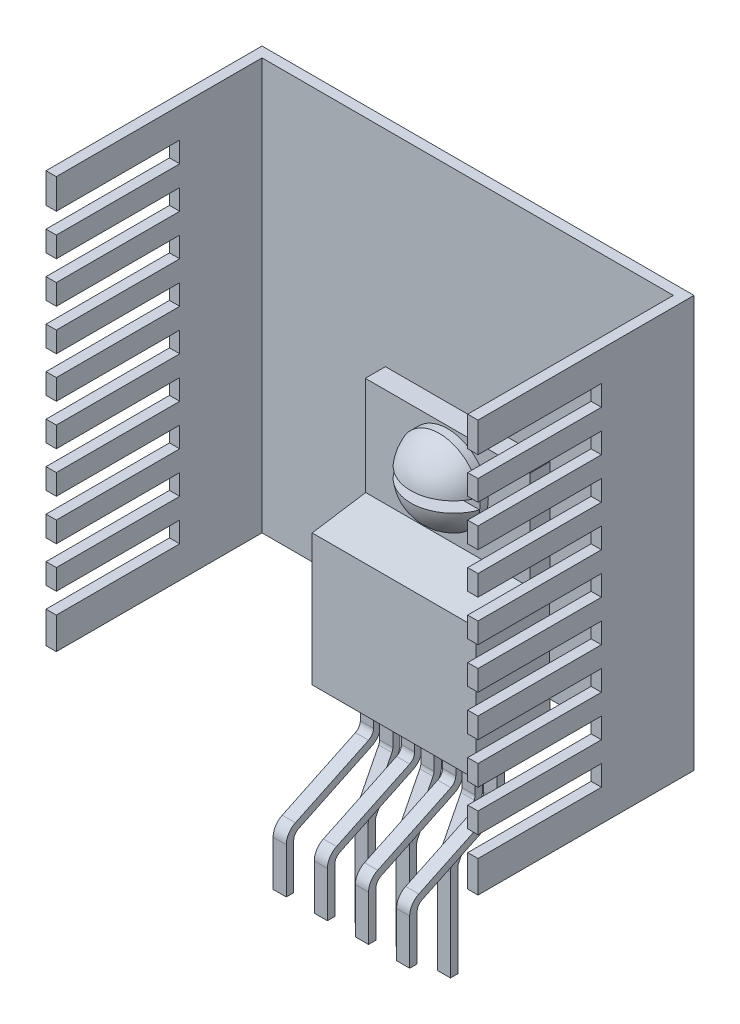
SolidWorks part; units mm, degrees
ref_plane "Front Plane" through (0, 0, 0) normal (0, 0, 1) x (1, 0, 0)
ref_plane "Top Plane" through (0, 0, 0) normal (0, 1, 0) x (1, 0, 0)
ref_plane "Right Plane" through (0, 0, 0) normal (1, 0, 0) x (0, 0, -1)
ref_plane "Plane2" through (0, 0, 1.397) normal (0, 0, 1) x (1, 0, 0)
ref_plane "Plane3" through (0, 6.35, 0) normal (0, 1, 0) x (-1, 0, 0)
ref_plane "Plane4" through (2.54, 0, 0) normal (1, 0, 0) x (0, 0, -1)
sketch "Sketch2" plane through (0, 6.35, 0) normal (0, 1, 0) x (-1, 0, 0)
  line L1 (1.27, -7.5946) -> (-8.89, -7.5946)
  line L2 (1.27, -7.5946) -> (1.27, -3.0226)
  line L3 (1.27, -3.0226) -> (-8.89, -3.0226)
  line L4 (-8.89, -7.5946) -> (-8.89, -3.0226)
  dimension "D1" = 10.16
  dimension "D2" = 4.572
  dimension "D3" = 1.27
  dimension "D4" = 7.5946
extrude "Base-Extrude" add sketch "Sketch2" along normal blind 14.732
sketch "Sketch3" plane through (-1.27, 0, 0) normal (-1, 0, 0) x (0, 0, 1)
  line L0 (-6.3246, 14.986) -> (-6.3246, 21.082)
  line L1 (-6.3246, 14.986) -> (-3.0226, 14.478)
  line L2 (-7.5946, 21.082) -> (-7.5946, 6.35) construction
  line L3 (-7.5946, 21.082) -> (-3.0226, 21.082) construction
  line L5 (-3.0226, 21.082) -> (-3.0226, 6.35) construction
  dimension "D1" = 1.27
  dimension "D2" = 6.096
  dimension "D3" = 6.604
extrude "Cut-Extrude1" cut sketch "Sketch3" against normal through all and the other way through all
sketch "Sketch5" plane through (-1.27, 0, 0) normal (-1, 0, 0) x (0, 0, 1)
  line L0 (-6.3246, 14.986) -> (-3.0226, 14.478) construction
  line L1 (-7.5946, 21.082) -> (-7.5946, 6.35) construction
  line L2 (-7.5946, 6.35) -> (-3.0226, 6.35) construction
  line L3 (-3.0226, 14.478) -> (-3.0226, 6.35) construction
  line L4 (-7.5946, 15.1814) -> (-3.0226, 14.478)
  line L5 (-7.5946, 15.1814) -> (-7.5946, 6.35)
  line L6 (-7.5946, 6.35) -> (-3.0226, 6.35)
  line L7 (-3.0226, 14.478) -> (-3.0226, 6.35)
extrude "Cut-Extrude4" cut sketch "Sketch5" against normal blind 0.0254
sketch "Sketch6" plane through (8.89, 0, 0) normal (1, 0, 0) x (0, 0, -1)
  line L0 (3.0226, 14.478) -> (6.3246, 14.986) construction
  line L1 (3.0226, 14.478) -> (3.0226, 6.35) construction
  line L2 (3.0226, 6.35) -> (7.5946, 6.35) construction
  line L3 (7.5946, 21.082) -> (7.5946, 6.35) construction
  line L4 (3.0226, 14.478) -> (7.5946, 15.1814)
  line L5 (3.0226, 14.478) -> (3.0226, 6.35)
  line L6 (3.0226, 6.35) -> (7.5946, 6.35)
  line L7 (7.5946, 15.1814) -> (7.5946, 6.35)
extrude "Cut-Extrude5" cut sketch "Sketch6" against normal blind 0.0254
sketch "Sketch7" plane through (0, 0, -7.5946) normal (0, 0, -1) x (-1, 0, 0)
  line L0 (-8.89, 21.082) -> (-8.89, 15.1814) construction
  line L1 (-8.89, 21.082) -> (1.27, 21.082) construction
  line L2 (1.27, 21.082) -> (1.27, 15.1814) construction
  line L3 (-8.89, 21.082) -> (-8.89, 15.1814)
  line L4 (-8.89, 21.082) -> (1.27, 21.082)
  line L5 (1.27, 21.082) -> (1.27, 15.1814)
  line L6 (-8.89, 15.1814) -> (-7.62, 15.1814)
  line L7 (-7.62, 15.1814) -> (-7.62, 9.652)
  line L8 (-7.62, 9.652) -> (0, 9.652)
  line L9 (0, 15.1814) -> (0, 9.652)
  line L10 (0, 15.1814) -> (1.27, 15.1814)
  line L11 (-8.8646, 6.35) -> (-8.8646, 15.1814) construction
  line L12 (-8.8646, 6.35) -> (1.2446, 6.35) construction
  line L13 (1.2446, 15.1814) -> (1.2446, 6.35) construction
  dimension "D1" = 1.2446
  dimension "D2" = 3.302
  dimension "D3" = 1.2446
extrude "Cut-Extrude6" cut sketch "Sketch7" against normal blind 0.0254
sketch "Sketch9" plane through (0, 0, 0) normal (1, 0, 0) x (0, 0, -1)
  line L0 (0, 0.254) -> (0, -2.54)
  line L2 (5.3848, 6.35) -> (5.3848, 3.7846)
  line L3 (50, 6.35) -> (-50, 6.35) construction
  line L4 (4.9509, 3.0969) -> (0.4339, 0.9417)
  arc A0 (4.9509, 3.0969) -> (5.3848, 3.7846) centre (4.6228, 3.7846) ccw
  arc A1 (0.4339, 0.9417) -> (0, 0.254) centre (0.762, 0.254) ccw
  dimension "D1" = 0.762
  dimension "D2" = 5.3848
  dimension "D3" = 2.5654
  dimension "D4" = 6.096
  dimension "D5" = 2.54
extrude "Boss-Extrude-Thin1" add sketch "Sketch9" along normal mid plane 0.8128 thin thin type two direction wall 0.2286 second wall 0.2286
pattern_linear "LPattern2" count 4 spacing 2.54 along (1, 0, 0) of "Boss-Extrude-Thin1"
ref_plane "Plane5" through (1.27, 0, 0) normal (1, 0, 0) x (0, 0, -1)
sketch "Sketch10" plane through (1.27, 0, 0) normal (1, 0, 0) x (0, 0, -1)
  line L0 (5.3086, 6.35) -> (5.3086, 3.4338)
  line L1 (50, 6.35) -> (-50, 6.35) construction
  line L2 (5.2258, 3.0884) -> (3.8674, 0.4168)
  line L3 (3.7846, 0.0714) -> (3.7846, -5.588)
  line L4 (7.5946, 6.35) -> (3.0226, 6.35) construction
  arc A0 (5.2258, 3.0884) -> (5.3086, 3.4338) centre (4.5466, 3.4338) ccw
  arc A1 (3.8674, 0.4168) -> (3.7846, 0.0714) centre (4.5466, 0.0714) ccw
  point P10 (5.3086, 3.2512)
  point P13 (3.7846, 0.254)
  dimension "D5" = 0.762
  dimension "D1" = 1.524
  dimension "D2" = 11.938
  dimension "D3" = 5.842
  dimension "D4" = 3.0988
extrude "Boss-Extrude-Thin2" add sketch "Sketch10" along normal mid plane 0.8128 thin thin type two direction wall 0.2286 second wall 0.2286
pattern_linear "LPattern3" count 3 spacing 2.54 along (1, 0, 0) of "Boss-Extrude-Thin2"
sketch "Sketch11" plane through (0, 21.082, 0) normal (0, 1, 0) x (-1, 0, 0)
  line L0 (-16.51, -7.5692) -> (8.89, -7.5692)
  line L1 (8.89, -7.5692) -> (8.89, 5.1308)
  line L2 (-16.51, -7.5692) -> (-16.51, 5.1308)
  line L3 (1.27, -7.5692) -> (-8.89, -7.5692) construction
  dimension "D1" = 25.4
  dimension "D2" = 8.89
  dimension "D3" = 12.7
extrude "Boss-Extrude-Thin3" add sketch "Sketch11" along normal blind 12.7 and the other way blind 12.7 thin thin type one direction reverse wall 0.635
sketch "Sketch4" plane through (0, 0, -6.3246) normal (0, 0, 1) x (1, 0, 0)
  line L1 (-1.27, 21.082) -> (8.89, 21.082) construction
  line L2 (3.81, 21.082) -> (3.81, 8.7865) construction
  circle A0 centre (3.81, 18.415) radius 1.905
  dimension "D1" = 3.81
  dimension "D2" = 2.667
extrude "Cut-Extrude2" cut sketch "Sketch4" against normal blind 14.732
sketch "Sketch12" plane through (17.145, 0, 0) normal (1, 0, 0) x (0, 0, -1)
  line L0 (-5.1308, 33.782) -> (-5.1308, 8.382) construction
  line L1 (2.4892, 31.9278) -> (-5.1308, 31.9278)
  line L2 (2.4892, 31.9278) -> (2.4892, 30.6578)
  line L3 (2.4892, 30.6578) -> (-5.1308, 30.6578)
  line L4 (-5.1308, 31.9278) -> (-5.1308, 30.6578)
  line L5 (8.2042, 33.782) -> (-5.1308, 33.782) construction
  line L6 (2.4892, 29.3878) -> (-5.1308, 29.3878)
  line L7 (2.4892, 29.3878) -> (2.4892, 28.1178)
  line L8 (2.4892, 28.1178) -> (-5.1308, 28.1178)
  line L9 (-5.1308, 29.3878) -> (-5.1308, 28.1178)
  line L10 (2.4892, 26.8478) -> (-5.1308, 26.8478)
  line L11 (2.4892, 26.8478) -> (2.4892, 25.5778)
  line L12 (2.4892, 25.5778) -> (-5.1308, 25.5778)
  line L13 (-5.1308, 26.8478) -> (-5.1308, 25.5778)
  line L14 (2.4892, 24.3078) -> (-5.1308, 24.3078)
  line L15 (2.4892, 24.3078) -> (2.4892, 23.0378)
  line L16 (2.4892, 23.0378) -> (-5.1308, 23.0378)
  line L17 (-5.1308, 24.3078) -> (-5.1308, 23.0378)
  line L18 (2.4892, 21.7678) -> (-5.1308, 21.7678)
  line L19 (2.4892, 21.7678) -> (2.4892, 20.4978)
  line L20 (2.4892, 20.4978) -> (-5.1308, 20.4978)
  line L21 (-5.1308, 21.7678) -> (-5.1308, 20.4978)
  line L22 (2.4892, 19.2278) -> (-5.1308, 19.2278)
  line L23 (2.4892, 19.2278) -> (2.4892, 17.9578)
  line L24 (2.4892, 17.9578) -> (-5.1308, 17.9578)
  line L25 (-5.1308, 19.2278) -> (-5.1308, 17.9578)
  line L26 (2.4892, 16.6878) -> (-5.1308, 16.6878)
  line L27 (2.4892, 16.6878) -> (2.4892, 15.4178)
  line L28 (2.4892, 15.4178) -> (-5.1308, 15.4178)
  line L29 (-5.1308, 16.6878) -> (-5.1308, 15.4178)
  line L30 (2.4892, 14.1478) -> (-5.1308, 14.1478)
  line L31 (2.4892, 14.1478) -> (2.4892, 12.8778)
  line L32 (2.4892, 12.8778) -> (-5.1308, 12.8778)
  line L33 (-5.1308, 14.1478) -> (-5.1308, 12.8778)
  line L34 (2.4892, 11.6078) -> (-5.1308, 11.6078)
  line L35 (2.4892, 11.6078) -> (2.4892, 10.3378)
  line L36 (2.4892, 10.3378) -> (-5.1308, 10.3378)
  line L37 (-5.1308, 11.6078) -> (-5.1308, 10.3378)
  dimension "D1" = 7.62
  dimension "D2" = 1.8542
  dimension "D3" = 1.27
  dimension "D4" = 1.27
  dimension "D5" = 1.27
  dimension "D6" = 1.27
  dimension "D7" = 1.27
  dimension "D8" = 1.27
  dimension "D9" = 1.27
  dimension "D10" = 1.27
  dimension "D11" = 1.27
extrude "Cut-Extrude7" cut sketch "Sketch12" against normal through all
sketch "Sketch13" plane through (0, 0, -6.3246) normal (0, 0, 1) x (1, 0, 0)
  circle A0 centre (3.81, 18.415) radius 2.5146
  dimension "D1" = 5.0292
extrude "Boss-Extrude1" add sketch "Sketch13" along normal blind 0.508
dome "Dome1" faces to dome 1 distance 1.778 reverse direction no elliptical dome no face at (6.3246, 18.415, -5.8166) parameters "D1"=1.778
ref_plane "Plane6" through (0, 0, -5.3086) normal (0, 0, 1) x (1, 0, 0)
sketch "Sketch14" plane through (0, 0, -5.3086) normal (0, 0, 1) x (1, 0, 0)
  line L0 (3.81, 18.415) -> (6.5058, 18.415) construction
  line L1 (0.5829, 18.7452) -> (6.5058, 18.7452)
  line L2 (0.5829, 18.7452) -> (0.5829, 18.0848)
  line L3 (0.5829, 18.0848) -> (6.5058, 18.0848)
  line L4 (6.5058, 18.7452) -> (6.5058, 18.0848)
  dimension "D1" = 0.6604
extrude "Cut-Extrude8" cut sketch "Sketch14" against normal blind 0.508 and the other way blind 3.556
sketch "Sketch15" plane through (0, 0, -8.2042) normal (0, 0, -1) x (-1, 0, 0)
  line L1 (-6.9509, 17.9036) -> (-4.9376, 15.4392)
  line L2 (-4.9376, 15.4392) -> (-1.7967, 15.9506)
  line L3 (-1.7967, 15.9506) -> (-0.6691, 18.9264)
  line L4 (-0.6691, 18.9264) -> (-2.6824, 21.3908)
  line L5 (-2.6824, 21.3908) -> (-5.8233, 20.8794)
  line L6 (-5.8233, 20.8794) -> (-6.9509, 17.9036)
  circle A0 centre (-3.81, 18.415) radius 2.7559 construction
  arc A2 (-6.3028, 18.0848) -> (-1.3172, 18.0848) centre (-3.81, 18.415) ccw construction
  dimension "D1" = 5.5118
extrude "Boss-Extrude2" add sketch "Sketch15" along normal blind 1.27
sketch "Sketch16" plane through (0, 0, -9.4742) normal (0, 0, -1) x (-1, 0, 0)
  circle A0 centre (-3.81, 18.415) radius 1.5875
  circle A1 centre (-3.81, 18.415) radius 2.5146 construction
  dimension "D1" = 3.175
extrude "Boss-Extrude3" add sketch "Sketch16" along normal blind 0.508
ref_axis "Axis1" through (3.81, 18.415, -16.7385) along (0, 0, 1)
ref_plane "Plane7" through (3.81, 0, 0) normal (1, 0, 0) x (0, 0, -1)
sketch "Sketch18" plane through (3.81, 0, 0) normal (1, 0, 0) x (0, 0, -1)
  line L0 (8.8682, 22.0807) -> (10.1184, 19.0412)
  line L1 (5.8166, 18.415) -> (6.3246, 18.415) construction
  line L2 (8.8682, 22.0807) -> (9.9311, 22.5179)
  line L3 (9.9311, 22.5179) -> (11.1813, 19.4783)
  line L4 (10.1184, 19.0412) -> (11.1813, 19.4783)
  line L5 (6.938, 18.415) -> (17.213, 18.415) construction
revolve "Cut-Revolve1" cut sketch "Sketch18" angle 360 about L5
ref_plane "Plane8" through (0, 0, 0) normal (0, 1, 0) x (-1, 0, 0)
sketch "Component_Outline" plane through (0, 0, 0) normal (0, 1, 0) x (-1, 0, 0)
  line L0 (-2.1336, -5.0494) -> (-2.1336, -0.5323) construction
  line L1 (1.27, -7.5692) -> (8.89, -7.5692)
  line L2 (-2.1336, 0.2286) -> (-2.9464, 0.2286)
  line L3 (-4.6736, 0.2286) -> (-5.4864, 0.2286)
  line L4 (8.89, -7.5692) -> (8.89, 5.1308)
  line L5 (-8.89, -7.5692) -> (-16.51, -7.5692)
  line L6 (-7.2136, 0.2286) -> (-8.0264, 0.2286)
  line L7 (1.2446, -3.0226) -> (1.27, -7.5692)
  line L8 (-16.51, -7.5692) -> (-16.51, 5.1308)
  line L9 (-8.8646, -3.0226) -> (-8.89, -7.5692)
  line L10 (-0.4064, 0.2286) -> (-0.4064, -3.0226)
  line L11 (-0.4064, -3.0226) -> (-2.1336, -3.0226)
  line L12 (-2.1336, 0.2286) -> (-2.1336, -3.0226)
  line L13 (1.2446, -3.0226) -> (-8.8646, -3.0226) construction
  line L14 (-4.6736, -5.0494) -> (-4.6736, -0.5323) construction
  line L16 (-2.9464, 0.2286) -> (-2.9464, -3.0226)
  line L17 (-2.9464, -3.0226) -> (-4.6736, -3.0226)
  line L18 (-4.6736, 0.2286) -> (-4.6736, -3.0226)
  line L19 (-7.2136, -5.0494) -> (-7.2136, -0.5323) construction
  line L21 (-5.4864, 0.2286) -> (-5.4864, -3.0226)
  line L22 (-5.4864, -3.0226) -> (-7.2136, -3.0226)
  line L23 (-7.2136, 0.2286) -> (-7.2136, -3.0226)
  line L24 (8.89, 5.1308) -> (9.525, 5.1308)
  line L26 (-8.0264, 0.2286) -> (-8.0264, -3.0226)
  line L27 (-8.0264, -3.0226) -> (-8.8646, -3.0226)
  line L29 (1.2446, -3.0226) -> (0.4064, -3.0226)
  line L32 (0.4064, -3.0226) -> (0.4064, 0.2286)
  line L33 (9.525, 5.1308) -> (9.525, -8.2042)
  line L34 (9.525, -8.2042) -> (-0.6691, -8.2042)
  line L35 (-0.6691, -8.2042) -> (-0.6691, -9.9822)
  line L36 (-16.51, 5.1308) -> (-17.145, 5.1308)
  line L37 (-17.145, 5.1308) -> (-17.145, -8.2042)
  line L38 (-17.145, -8.2042) -> (-6.9509, -8.2042)
  line L39 (-6.9509, -8.2042) -> (-6.9509, -9.9822)
  line L40 (-0.6691, -9.9822) -> (-6.9509, -9.9822)
  line L41 (-4.7673, -9.9822) -> (-2.8527, -9.9822) construction
  line L42 (0.4064, 0.2286) -> (-0.4064, 0.2286)
